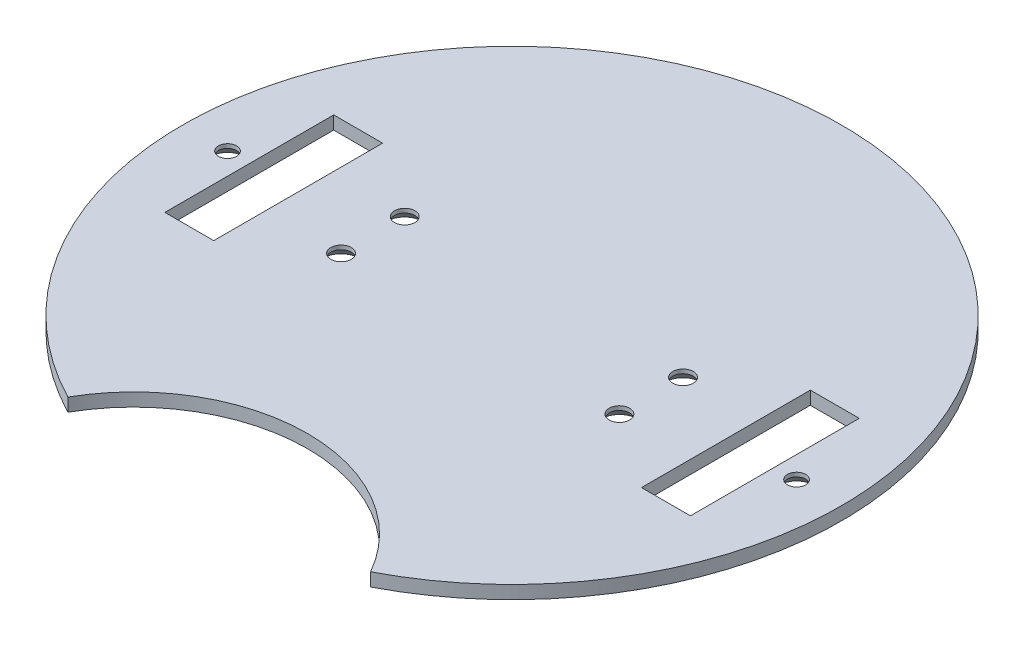
SolidWorks part; units mm, degrees
ref_plane "Front Plane" through (0, 0, 0) normal (0, 0, 1) x (1, 0, 0)
ref_plane "Top Plane" through (0, 0, 0) normal (0, 1, 0) x (1, 0, 0)
ref_plane "Right Plane" through (0, 0, 0) normal (1, 0, 0) x (0, 0, -1)
sketch "Sketch1" plane through (0, 0, 0) normal (0, 1, 0) x (1, 0, 0)
  line L0 (0, -83.2398) -> (-33.2911, -64.4046) construction
  line L1 (0, -83.2398) -> (0, 0) construction
  arc A0 (33.2911, -64.4046) -> (-33.2911, -64.4046) centre (0, 0) ccw
  arc A1 (33.2911, -64.4046) -> (-33.2911, -64.4046) centre (0, -83.2398) ccw
  dimension "D1" = 145
  dimension "D2" = 76.5
  dimension "D3" = 60.5
extrude "Boss-Extrude1" add sketch "Sketch1" along normal blind 2.9
sketch "solenoid placement" plane through (0, 2.9, 0) normal (0, 1, 0) x (1, 0, 0)
  line L0 (0, 0) -> (0, -36) construction
  line L1 (0, -36) -> (0, -44.9898) construction
  line L2 (-19, -36) -> (19, -36)
  line L3 (-19, -36) -> (-19, 28.4)
  line L4 (-19, 28.4) -> (19, 28.4)
  line L5 (19, -36) -> (19, 28.4)
  circle A1 centre (0, 0) radius 72.5 construction
  arc A2 (33.2911, -64.4046) -> (-33.2911, -64.4046) centre (0, 0) ccw construction
  arc A3 (33.2911, -64.4046) -> (-33.2911, -64.4046) centre (0, -83.2398) ccw construction
  dimension "D1" = 64.4
  dimension "D2" = 36
  dimension "D4" = 38
sketch "Sketch2" plane through (0, 2.9, 0) normal (0, 1, 0) x (1, 0, 0)
  line L1 (-57.5, 18.2695) -> (-47.34, 18.2695) construction
  line L2 (-57.5, 18.2695) -> (-57.5, -18.2695) construction
  line L3 (-57.5, -18.2695) -> (-47.34, -18.2695) construction
  line L4 (-47.34, 18.2695) -> (-47.34, -18.2695) construction
  line L8 (-57.8, -18.5695) -> (-47.04, -18.5695)
  line L9 (-47.04, 18.5695) -> (-47.04, -18.5695)
  line L10 (-57.8, 18.5695) -> (-47.04, 18.5695)
  line L11 (-57.8, 18.5695) -> (-57.8, -18.5695)
  line L12 (0, 0) -> (0, 72.5) construction
  line L13 (47.34, 18.2695) -> (47.34, -18.2695) construction
  line L14 (57.5, -18.2695) -> (47.34, -18.2695) construction
  line L15 (57.5, 18.2695) -> (57.5, -18.2695) construction
  line L16 (57.5, 18.2695) -> (47.34, 18.2695) construction
  line L17 (57.8, 18.5695) -> (57.8, -18.5695)
  line L18 (57.8, 18.5695) -> (47.04, 18.5695)
  line L19 (47.04, 18.5695) -> (47.04, -18.5695)
  line L20 (57.8, -18.5695) -> (47.04, -18.5695)
  arc A0 (33.2911, -64.4046) -> (-33.2911, -64.4046) centre (0, 0) ccw construction
extrude "Cut-Extrude1" cut sketch "Sketch2" against normal through all
sketch "Sketch3" plane through (0, 0, 0) normal (0, -1, 0) x (1, 0, 0)
  line L0 (0, 0) -> (0, -72.5) construction
  circle A0 centre (-62.58, 0) radius 2
  circle A1 centre (-30.61, 7) radius 2.25
  circle A2 centre (-30.61, -7) radius 2.25
  arc A3 (-33.2911, 64.4046) -> (33.2911, 64.4046) centre (0, 0) ccw construction
  circle A4 centre (30.61, -7) radius 2.25
  circle A5 centre (30.61, 7) radius 2.25
  circle A6 centre (62.58, 0) radius 2
  dimension "D1" = 4
  dimension "D2" = 4.5
extrude "Cut-Extrude2" cut sketch "Sketch3" against normal through all
chamfer "Chamfer1" distance 2 angle 41 6 edges at (-30.61, 0, -9.25) (-30.61, 0, 4.75) (-62.58, 0, -2) (62.58, 0, 2) (30.61, 0, 9.25) (30.61, 0, -4.75) first distance on face at (-30.61, 2.9, -9.25) first distance on face at (-30.61, 2.9, 4.75) first distance on face at (-62.58, 2.9, -2) first distance on face at (62.58, 2.9, 2) first distance on face at (30.61, 2.9, 9.25) first distance on face at (30.61, 2.9, -4.75)
equation "\"smallPulleyTeeth\"= 15"
equation "\"largePulleyTeeth\"= 30"
equation "\"eighthThick\"= 2.9mm"
equation "\"sixteenthThick\" = 1.7mm"
equation "\"quarterThick\"=5.9mm"
equation "\"OD\" = 145mm"
equation "\"puckAngle\" = 60.5deg"
equation "\"D1@Sketch1\"=\"OD\""
equation "\"puckDiam\" = 76.5mm"
equation "\"D2@Sketch1\"=\"puckDiam\""
equation "\"D3@Sketch1\"=\"puckAngle\""
equation "\"D1@Boss-Extrude1\"=\"eighthThick\""
equation "\"axlePress\" = 5.9mm"
equation "\"press\" = 0.2mm"
equation "\"wheelClear\" = 0.3mm"
equation "\"D1@Sketch2\"=\"wheelClear\""
equation "\"10-32clear\" = 4.5mm"
equation "\"6-32clear\" = 3.3mm"
equation "\"8-32clear\" = 4.0mm"
equation "\"wheelHeight\" = 24mm"
equation "\"D1@Sketch3\"=\"8-32clear\""
equation "\"D2@Sketch3\"=\"10-32clear\""
